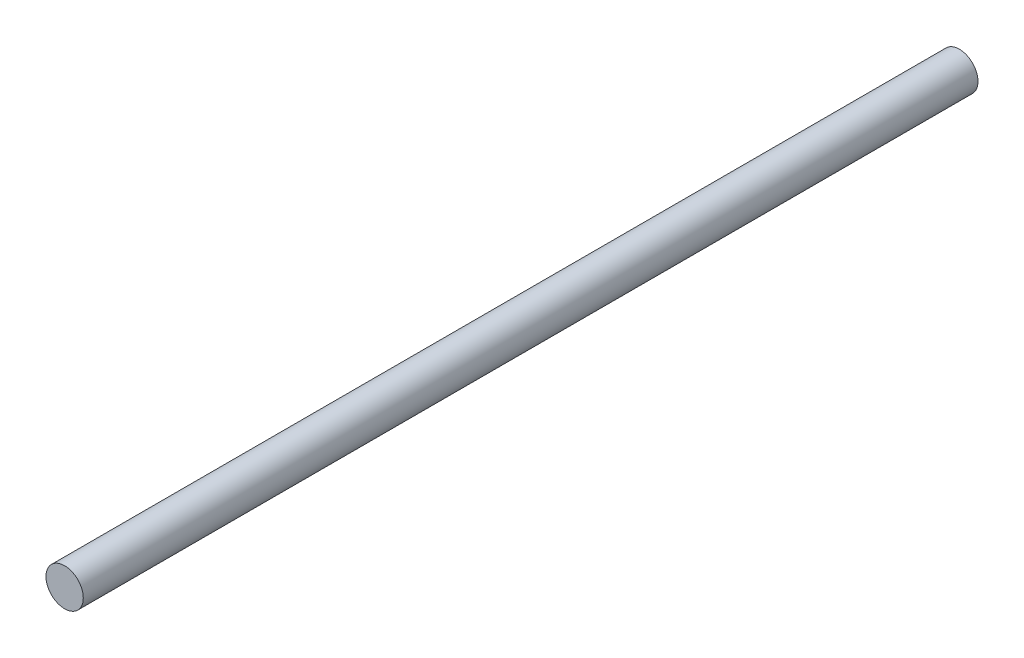
SolidWorks part; units mm, degrees
ref_plane "Front Plane" through (0, 0, 0) normal (0, 0, 1) x (1, 0, 0)
ref_plane "Top Plane" through (0, 0, 0) normal (0, 1, 0) x (1, 0, 0)
ref_plane "Right Plane" through (0, 0, 0) normal (1, 0, 0) x (0, 0, -1)
sketch "Sketch1" plane through (0, 0, 0) normal (0, 0, 1) x (1, 0, 0)
  circle A0 centre (0, 0) radius 3.175
extrude "Boss-Extrude1" add sketch "Sketch1" along normal blind 152.24 contours A0
